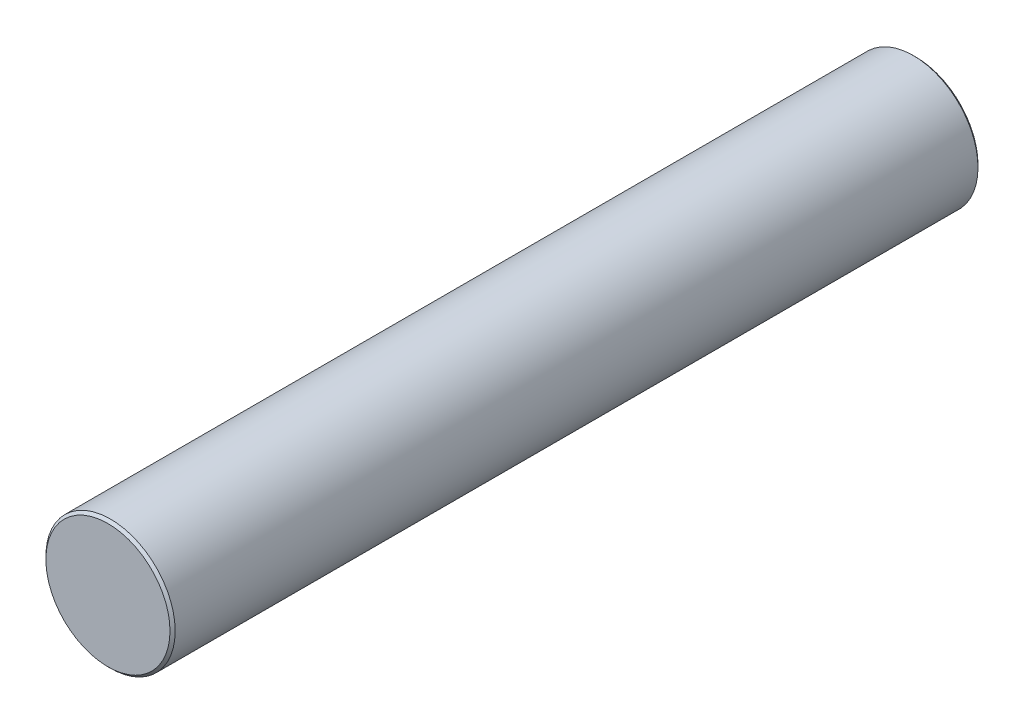
SolidWorks part; units mm, degrees
material "AISI 316 Stainless Steel Sheet (SS)"
ref_plane "Front Plane" through (0, 0, 0) normal (0, 0, 1) x (1, 0, 0)
ref_plane "Top Plane" through (0, 0, 0) normal (0, 1, 0) x (1, 0, 0)
ref_plane "Right Plane" through (0, 0, 0) normal (1, 0, 0) x (0, 0, -1)
sketch "Sketch1" plane through (0, 0, 0) normal (1, 0, 0) x (0, 0, -1)
  line L0 (-25, 0) -> (25, 0) construction
  line L1 (0, -4) -> (0, 4) construction
  point P4 (0, 0)
  point P8 (0, 0)
sketch "Sketch2" plane through (0, 0, 0) normal (0, 0, 1) x (1, 0, 0)
  circle A0 centre (0, 0) radius 4
extrude "Boss-Extrude1" add sketch "Sketch2" along normal up to vertex (25 mm away) and the other way up to vertex (25 mm away) up to point (0, 0, 25) other way up to point (0, 0, -25)
chamfer "Chamfer1" distance 0.16 angle 45 2 edges at (4, 0, -25) (4, 0, 25)
equation "\"D1@Chamfer1\"=\"Diameter@Sketch1\"*.02"
